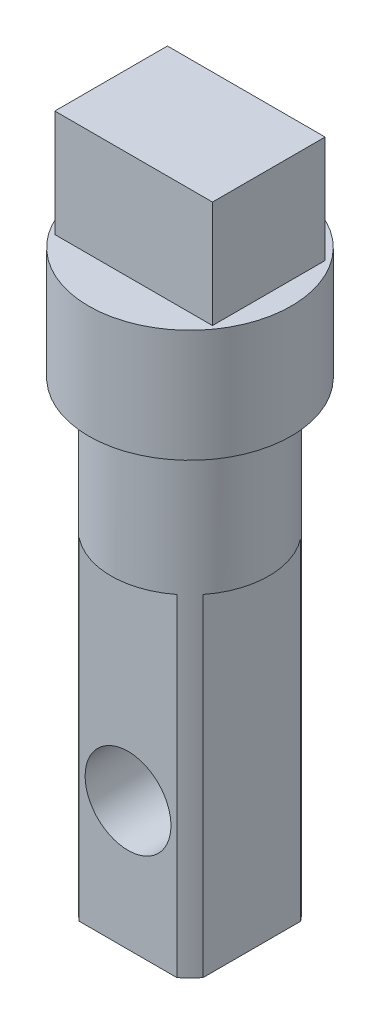
SolidWorks part; units mm, degrees
ref_plane "Front Plane" through (0, 0, 0) normal (0, 0, 1) x (1, 0, 0)
ref_plane "Top Plane" through (0, 0, 0) normal (0, 1, 0) x (1, 0, 0)
ref_plane "Right Plane" through (0, 0, 0) normal (1, 0, 0) x (0, 0, -1)
sketch "Sketch1" plane through (0, 0, 0) normal (0, 1, 0) x (1, 0, 0)
  circle A0 centre (0, 0) radius 7
  dimension "D1" = 14
extrude "Boss-Extrude1" add sketch "Sketch1" along normal blind 46.228
sketch "Sketch2" plane through (0, 46.228, 0) normal (0, 1, 0) x (1, 0, 0)
  circle A0 centre (0, 0) radius 9
  dimension "D1" = 18
extrude "Boss-Extrude2" add sketch "Sketch2" along normal mid plane 10
sketch "Sketch3" plane through (0, 51.228, 0) normal (0, 1, 0) x (1, 0, 0)
  line L1 (-7, 5) -> (7, 5)
  line L2 (-7, 5) -> (-7, -5)
  line L3 (-7, -5) -> (7, -5)
  line L4 (7, 5) -> (7, -5)
  line L5 (-7, 5) -> (7, -5) construction
  line L6 (-7, -5) -> (7, 5) construction
  point P0 (0, 0)
  dimension "D1" = 10
  dimension "D2" = 14
extrude "Boss-Extrude3" add sketch "Sketch3" along normal blind 9.5 contours L2 L3 L4 L1
sketch "Sketch4" plane through (0, 0, 0) normal (0, 1, 0) x (1, 0, 0)
  line L1 (-5.5, -5.5) -> (5.5, -5.5)
  line L2 (-5.5, -5.5) -> (-5.5, 5.5)
  line L3 (-5.5, 5.5) -> (5.5, 5.5)
  line L4 (5.5, -5.5) -> (5.5, 5.5)
  line L5 (-5.5, -5.5) -> (5.5, 5.5) construction
  line L6 (-5.5, 5.5) -> (5.5, -5.5) construction
  point P0 (0, 0)
  dimension "D1" = 11
  dimension "D2" = 11
extrude "Cut-Extrude1" cut sketch "Sketch4" along normal blind 29.464 flip side to cut
ref_axis "Axis1" through (0, -3.8365, 0) along (0, 1, 0)
sketch "Sketch5" plane through (0, 0, -5.5) normal (0, 0, -1) x (-1, 0, 0)
  line L0 (0, -3.8365) -> (0, 63.8025) construction
  line L1 (-4.3301, 29.464) -> (4.3301, 29.464) construction
  circle A0 centre (0, 11.43) radius 3.81
  dimension "D2" = 7.62
  dimension "D1" = 18.034
extrude "Cut-Extrude2" cut sketch "Sketch5" against normal through all
